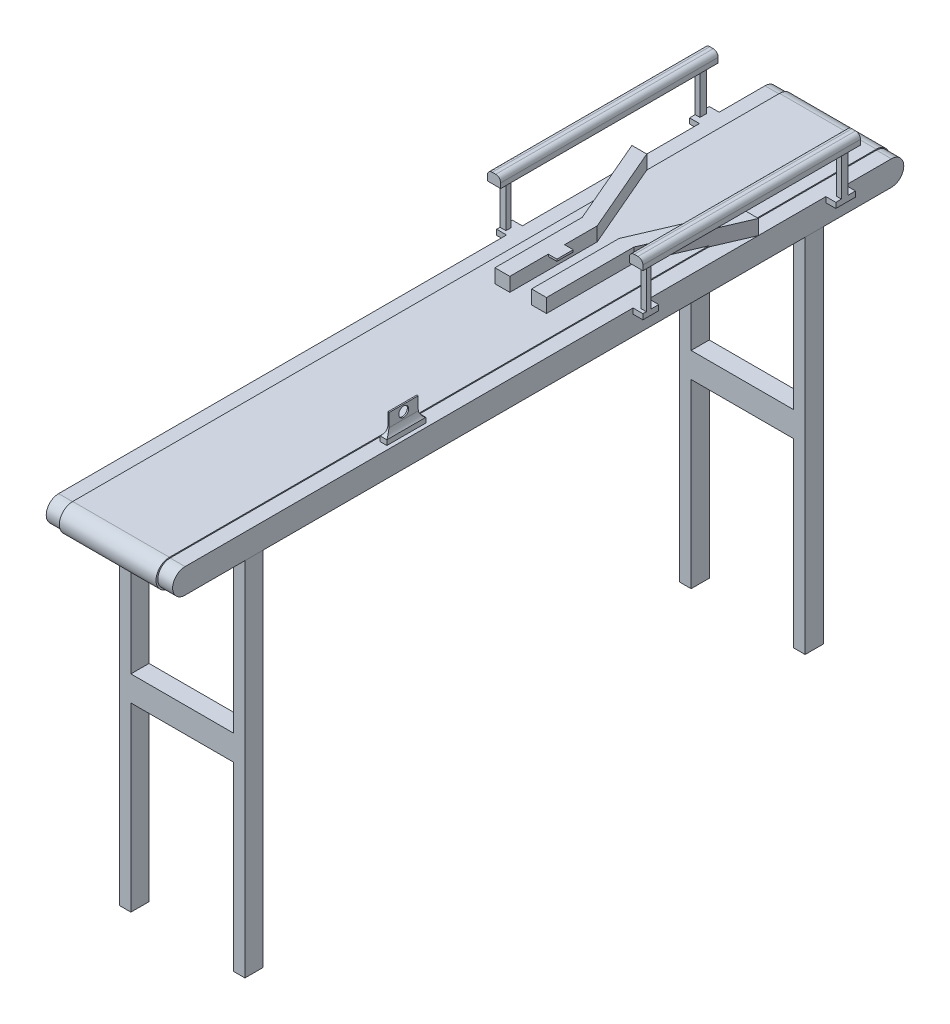
SolidWorks part; units mm, degrees
ref_plane "Alzado" through (0, 0, 0) normal (0, 0, 1) x (1, 0, 0)
ref_plane "Planta" through (0, 0, 0) normal (0, 1, 0) x (1, 0, 0)
ref_plane "Vista lateral" through (0, 0, 0) normal (1, 0, 0) x (0, 0, -1)
sketch "Croquis1" plane through (0, 0, 0) normal (0, 1, 0) x (1, 0, 0)
  line L1 (0, 0) -> (-255, 0)
  line L2 (0, 0) -> (0, 1475)
  line L3 (0, 1475) -> (-255, 1475)
  line L4 (-255, 0) -> (-255, 1475)
  dimension "D1" = 255
  dimension "D2" = 1475
extrude "Saliente-Extruir1" add sketch "Croquis1" along normal blind 50
sketch "Croquis2" plane through (-255, 0, 0) normal (-1, 0, 0) x (0, 0, 1)
  line L0 (6.4584, -12.3806) -> (-25, 0)
  line L4 (-1481.2344, 62.3806) -> (-1449.776, 50)
  line L8 (-1449.776, 0) -> (-1480.215, -12.0359)
  line L9 (-1480.215, -12.0359) -> (-1481.2344, 62.3806)
  line L11 (-25, 50) -> (5.439, 62.0359)
  line L12 (5.439, 62.0359) -> (6.4584, -12.3806)
  line L13 (-1475, 0) -> (0, 0) construction
  arc A4 (-25, 50) -> (-25, 0) centre (-25, 25) cw
  arc A5 (-1449.776, 0) -> (-1449.776, 50) centre (-1449.776, 25) cw
extrude "Cortar-Extruir1" cut sketch "Croquis2" against normal through all
sketch "Croquis5" plane through (-255, 0, 0) normal (-1, 0, 0) x (0, 0, 1)
  line L0 (-1449.776, 0) -> (-25, 0) construction
  line L2 (-1449.276, 52) -> (-23.5, 52)
  line L3 (-23.5, -2) -> (-1449.276, -2)
  arc A1 (-23.5, -2) -> (-23.5, 52) centre (-23.5, 25) ccw
  arc A2 (-25, 0) -> (-25, 50) centre (-25, 25) ccw construction
  arc A3 (-1449.276, 52) -> (-1449.276, -2) centre (-1449.276, 25) ccw
  arc A5 (-1449.776, 50) -> (-1449.776, 0) centre (-1449.776, 25) ccw construction
  point P18 (-1474.776, 25)
  point P19 (-1476.276, 25)
  dimension "D1" = 27
  dimension "D3" = 1.5
  dimension "D5" = 27
  dimension "D2" = 25
  dimension "D4" = 25
  dimension "D6" = 1.5
extrude "Saliente-Extruir2" add sketch "Croquis5" against normal blind 195 from offset 30 offset against normal yes
sketch "Croquis6" plane through (0, 0, 0) normal (0, -1, 0) x (1, 0, 0)
  line L0 (-255, -1449.776) -> (-255, -25) construction
  line L1 (-255, -147.7299) -> (-231.9101, -147.7299)
  line L2 (-255, -147.7299) -> (-255, -184.3095)
  line L3 (-255, -184.3095) -> (-231.9101, -184.3095)
  line L4 (-231.9101, -147.7299) -> (-231.9101, -184.3095)
  line L5 (-25, -147.7299) -> (-25, -184.3095)
  line L6 (-25, -147.7299) -> (-1.9101, -147.7299)
  line L7 (-1.9101, -147.7299) -> (-1.9101, -184.3095)
  line L8 (-25, -184.3095) -> (-1.9101, -184.3095)
  line L9 (-25, -1277.7299) -> (-25, -1314.3095)
  line L10 (-25, -1277.7299) -> (-1.9101, -1277.7299)
  line L11 (-1.9101, -1277.7299) -> (-1.9101, -1314.3095)
  line L12 (-25, -1314.3095) -> (-1.9101, -1314.3095)
  line L13 (-255, -1277.7299) -> (-255, -1314.3095)
  line L14 (-255, -1277.7299) -> (-231.9101, -1277.7299)
  line L15 (-231.9101, -1277.7299) -> (-231.9101, -1314.3095)
  line L16 (-255, -1314.3095) -> (-231.9101, -1314.3095)
  dimension "D1" = 2
  dimension "D2" = 2
extrude "Saliente-Extruir3" add sketch "Croquis6" along normal blind 731
sketch "Croquis7" plane through (-1.9101, 0, 0) normal (1, 0, 0) x (0, 0, -1)
  line L0 (147.7299, -731) -> (147.7299, 0) construction
  line L1 (147.7299, -314.7831) -> (184.3095, -314.7831)
  line L2 (147.7299, -314.7831) -> (147.7299, -365.5)
  line L3 (147.7299, -365.5) -> (184.3095, -365.5)
  line L4 (184.3095, -314.7831) -> (184.3095, -365.5)
  line L5 (184.3095, -731) -> (184.3095, 0) construction
  line L6 (1277.7299, -731) -> (1277.7299, 0) construction
  line L7 (1277.7299, -365.5) -> (1314.3095, -365.5)
  line L8 (1277.7299, -365.5) -> (1277.7299, -314.7831)
  line L9 (1277.7299, -314.7831) -> (1314.3095, -314.7831)
  line L10 (1314.3095, -365.5) -> (1314.3095, -314.7831)
  line L11 (1314.3095, -731) -> (1314.3095, 0) construction
extrude "Saliente-Extruir4" add sketch "Croquis7" against normal through all
sketch "Croquis9" plane through (-255, 0, 0) normal (-1, 0, 0) x (0, 0, 1)
  line L0 (-1449.776, 50) -> (-25, 50) construction
  line L1 (-1357.4324, 50) -> (-1317.6624, 50)
  line L2 (-1357.4324, 50) -> (-1357.4324, 39.2137)
  line L3 (-1357.4324, 39.2137) -> (-1317.6624, 39.2137)
  line L4 (-1317.6624, 50) -> (-1317.6624, 39.2137)
  line L5 (-1449.776, 50) -> (-25, 50) construction
  line L6 (-960.3915, 50) -> (-928.5918, 50)
  line L7 (-960.3915, 50) -> (-960.3915, 39.2137)
  line L8 (-960.3915, 39.2137) -> (-928.5918, 39.2137)
  line L9 (-928.5918, 50) -> (-928.5918, 39.2137)
extrude "Saliente-Extruir5" add sketch "Croquis9" against normal blind 275 and the other way blind 20
sketch "Croquis10" plane through (0, 50, 0) normal (0, 1, 0) x (1, 0, 0)
  line L0 (-275, 1317.6624) -> (-275, 1357.4324) construction
  line L1 (-275, 1342.1015) -> (-265.3595, 1342.1015)
  line L2 (-275, 1342.1015) -> (-275, 1328.9734)
  line L3 (-275, 1328.9734) -> (-265.3595, 1328.9734)
  line L4 (-265.3595, 1342.1015) -> (-265.3595, 1328.9734)
  line L5 (20, 1317.6624) -> (20, 1357.4324) construction
  line L6 (20, 1342.1015) -> (9.6893, 1342.1015)
  line L7 (20, 1342.1015) -> (20, 1328.9734)
  line L8 (20, 1328.9734) -> (9.6893, 1328.9734)
  line L9 (9.6893, 1342.1015) -> (9.6893, 1328.9734)
  line L10 (-275, 928.5918) -> (-275, 960.3915) construction
  line L11 (-275, 945.8609) -> (-263.0957, 945.8609)
  line L12 (-275, 945.8609) -> (-275, 935.4336)
  line L13 (-275, 935.4336) -> (-263.0957, 935.4336)
  line L14 (-263.0957, 945.8609) -> (-263.0957, 935.4336)
  line L15 (20, 928.5918) -> (20, 960.3915) construction
  line L16 (20, 944.4917) -> (9.6893, 944.4917)
  line L17 (20, 944.4917) -> (20, 935.4336)
  line L18 (20, 935.4336) -> (9.6893, 935.4336)
  line L19 (9.6893, 944.4917) -> (9.6893, 935.4336)
extrude "Saliente-Extruir6" add sketch "Croquis10" along normal blind 85
sketch "Croquis11" plane through (0, 135, 0) normal (0, 1, 0) x (1, 0, 0)
  line L1 (-283.985, 1357.4324) -> (-256.9224, 1357.4324)
  line L2 (-283.985, 1357.4324) -> (-283.985, 918.6217)
  line L3 (-283.985, 918.6217) -> (-256.9224, 918.6217)
  line L4 (-256.9224, 1357.4324) -> (-256.9224, 918.6217)
  line L5 (29.9826, 1357.4324) -> (2.5883, 1357.4324)
  line L6 (29.9826, 1357.4324) -> (29.9826, 918.6217)
  line L7 (29.9826, 918.6217) -> (2.5883, 918.6217)
  line L8 (2.5883, 1357.4324) -> (2.5883, 918.6217)
extrude "Saliente-Extruir7" add sketch "Croquis11" along normal blind 20
fillet "Redondeo1" radius 10 4 edges at (-283.985, 155, -1138.027) (-256.9224, 155, -1138.027) (29.9826, 155, -1138.027) (2.5883, 155, -1138.027)
sketch "Croquis12" plane through (0, 50, 0) normal (0, 1, 0) x (1, 0, 0)
  line L0 (-225, 1181.4075) -> (-149.5, 1005.7913)
  line L1 (-225, 23.5) -> (-225, 1449.276) construction
  line L2 (-105.5, 1005.7913) -> (-75.5, 1005.7913)
  line L3 (-105.5, 1005.7913) -> (-30, 1181.4075)
  line L4 (-30, 23.5) -> (-30, 1449.276) construction
  line L5 (-30, 1181.4075) -> (0, 1181.4075)
  line L6 (0, 1181.4075) -> (-75.5, 1005.7913)
  line L7 (-225, 1181.4075) -> (-255, 1181.4075)
  line L8 (-255, 1181.4075) -> (-179.5, 1005.7913)
  line L9 (-179.5, 1005.7913) -> (-149.5, 1005.7913)
  dimension "D1" = 119.5
  dimension "D2" = 119.5
  dimension "D3" = 30
  dimension "D4" = 30
  dimension "D5" = 30
  dimension "D6" = 30
extrude "Saliente-Extruir8" add sketch "Croquis12" along normal blind 30
sketch "Croquis13" plane through (0, 50, 0) normal (0, 1, 0) x (1, 0, 0)
  line L0 (-179.5, 829.5827) -> (-149.5, 829.5827)
  line L2 (-149.5, 1005.7913) -> (-149.5, 829.5827)
  line L4 (-105.5, 1005.7913) -> (-105.5, 829.5827)
  line L6 (-179.5, 1005.7913) -> (-179.5, 829.5827)
  line L8 (-75.5, 1005.7913) -> (-75.5, 829.5827)
  line L9 (-105.5, 829.5827) -> (-75.5, 829.5827)
  line L10 (-105.5, 1005.7913) -> (-75.5, 1005.7913)
  line L11 (-179.5, 1005.7913) -> (-149.5, 1005.7913)
extrude "Saliente-Extruir9" add sketch "Croquis13" along normal blind 30
sketch "Croquis14" plane through (0, 80, 0) normal (0, 1, 0) x (1, 0, 0)
  line L0 (-149.5, 1005.7913) -> (-149.5, 829.5827) construction
  line L1 (-149.5, 940.0062) -> (-132.0595, 940.0062)
  line L2 (-149.5, 940.0062) -> (-149.5, 907.1782)
  line L3 (-149.5, 907.1782) -> (-132.0595, 907.1782)
  line L4 (-132.0595, 940.0062) -> (-132.0595, 907.1782)
extrude "Saliente-Extruir10" add sketch "Croquis14" against normal blind 4
sketch "Croquis15" plane through (-255, 0, 0) normal (-1, 0, 0) x (0, 0, 1)
  line L0 (-147.7299, -731) -> (-147.7299, 0) construction
  line L1 (-235.8987, 13.8968) -> (-147.7299, 13.8968)
  line L2 (-235.8987, 13.8968) -> (-235.8987, -115.0214)
  line L3 (-235.8987, -115.0214) -> (-147.7299, -115.0214)
  line L4 (-147.7299, 13.8968) -> (-147.7299, -115.0214)
extrude "Saliente-Extruir11" add sketch "Croquis15" along normal blind 10
sketch "Croquis16" plane through (-265, 0, 0) normal (-1, 0, 0) x (0, 0, 1)
  line L1 (-197.1399, -72.2874) -> (-186.4887, -72.2874)
  line L2 (-197.1399, -72.2874) -> (-197.1399, -96.8099)
  line L3 (-197.1399, -96.8099) -> (-186.4887, -96.8099)
  line L4 (-186.4887, -72.2874) -> (-186.4887, -96.8099)
  line L5 (-147.7299, 13.8968) -> (-235.8987, 13.8968) construction
  circle A0 centre (-191.8143, -27.701) radius 2.5
  point P6 (-191.8143, -72.2874)
  point P10 (-191.8143, 13.8968)
  dimension "D1" = 5
extrude "Saliente-Extruir12" add sketch "Croquis16" along normal blind 5
sketch "Croquis17" plane through (-265, 0, 0) normal (-1, 0, 0) x (0, 0, 1)
  line L0 (-147.7299, 13.8968) -> (-235.8987, 13.8968) construction
  line L1 (-220.8987, -33.9032) -> (-162.7299, -33.9032)
  line L2 (-220.8987, -33.9032) -> (-220.8987, -47.8568)
  line L3 (-220.8987, -47.8568) -> (-162.7299, -47.8568)
  line L4 (-162.7299, -33.9032) -> (-162.7299, -47.8568)
  line L6 (-235.8987, 13.8968) -> (-235.8987, -115.0214) construction
  line L7 (-147.7299, -115.0214) -> (-147.7299, 13.8968) construction
  dimension "D1" = 47.8
  dimension "D2" = 15
  dimension "D3" = 15
extrude "Saliente-Extruir13" add sketch "Croquis17" along normal blind 2
sketch "Croquis18" plane through (-267, 0, 0) normal (-1, 0, 0) x (0, 0, 1)
  line L0 (-162.7299, -47.8568) -> (-162.7299, -33.9032) construction
  line L1 (-220.8987, -33.9032) -> (-162.7299, -33.9032)
  line L2 (-220.8987, -33.9032) -> (-220.8987, -35.9032)
  line L3 (-220.8987, -35.9032) -> (-162.7299, -35.9032)
  line L4 (-162.7299, -33.9032) -> (-162.7299, -35.9032)
  dimension "D1" = 2
extrude "Saliente-Extruir14" add sketch "Croquis18" along normal blind 40
sketch "Croquis19" plane through (0, 50, 0) normal (0, 1, 0) x (1, 0, 0)
  line L1 (-21.3436, 518.6251) -> (-7.8803, 518.6251)
  line L2 (-21.3436, 518.6251) -> (-21.3436, 440.089)
  line L3 (-21.3436, 440.089) -> (-7.8803, 440.089)
  line L4 (-7.8803, 518.6251) -> (-7.8803, 440.089)
extrude "Saliente-Extruir15" add sketch "Croquis19" along normal blind 10
sketch "Croquis20" plane through (0, 60, 0) normal (0, 1, 0) x (1, 0, 0)
  line L0 (-7.8803, 518.6251) -> (-21.3436, 518.6251) construction
  line L1 (-15.9519, 450.0636) -> (-13.2719, 450.0636)
  line L2 (-15.9519, 450.0636) -> (-15.9519, 508.6505)
  line L3 (-15.9519, 508.6505) -> (-13.2719, 508.6505)
  line L4 (-13.2719, 450.0636) -> (-13.2719, 508.6505)
  line L5 (-7.8803, 440.089) -> (-7.8803, 518.6251) construction
  point P6 (-14.6119, 518.6251)
  point P7 (-14.6119, 450.0636)
  point P10 (-7.8803, 479.3571)
  point P11 (-13.2719, 479.3571)
  point P12 (-13.2719, 556.381)
  point P13 (-13.2719, 508.6505)
  dimension "D1" = 2.68
extrude "Saliente-Extruir16" add sketch "Croquis20" along normal blind 40
fillet "Redondeo2" radius 20 4 edges at (-14.6119, 60, -450.0636) (-13.2719, 60, -479.3571) (-14.6119, 60, -508.6505) (-15.9519, 60, -479.3571)
sketch "Croquis21" plane through (-13.2719, 0, 0) normal (1, 0, 0) x (0, 0, -1)
  line L0 (508.6505, 100) -> (450.0636, 100) construction
  circle A0 centre (479.3571, 86.8446) radius 10
  point P5 (479.3571, 100)
  dimension "D1" = 20
extrude "Cortar-Extruir2" cut sketch "Croquis21" against normal blind 40
